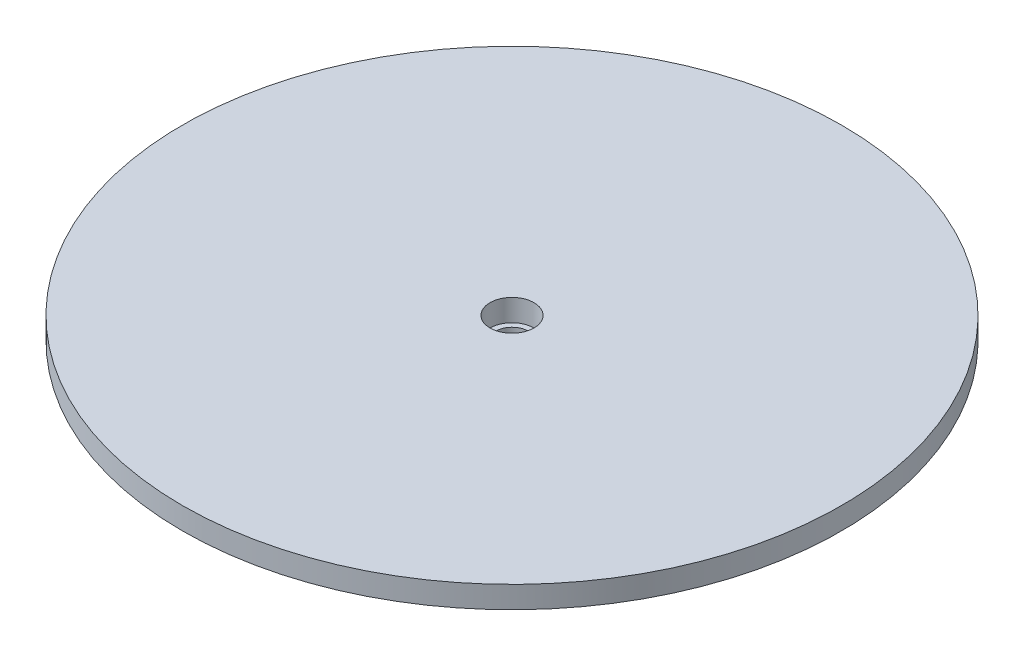
SolidWorks part; units mm, degrees
ref_plane "前视基准面" through (0, 0, 0) normal (0, 0, 1) x (1, 0, 0)
ref_plane "上视基准面" through (0, 0, 0) normal (0, 1, 0) x (1, 0, 0)
ref_plane "右视基准面" through (0, 0, 0) normal (1, 0, 0) x (0, 0, -1)
other "Configuration Table"
sketch "草图1" plane through (0, 0, 0) normal (0, 1, 0) x (1, 0, 0)
  circle A0 centre (0, 0) radius 10
  circle A1 centre (0, 0) radius 30
  circle A2 centre (0, 0) radius 2
  circle A3 centre (0, 0) radius 1
  circle A4 centre (0, 0) radius 1.5
  dimension "D3" = 20
  dimension "D5" = 3
  dimension "D1" = 60
  dimension "D2" = 2
  dimension "D4" = 4
extrude "凸台-拉伸1" add sketch "草图1" along normal blind 2 contours A1
sketch "草图2" plane through (0, 0, 0) normal (0, -1, 0) x (1, 0, 0)
  line L1 (-3, -3) -> (3, -3)
  line L2 (-3, -3) -> (-3, 3)
  line L3 (-3, 3) -> (3, 3)
  line L4 (3, -3) -> (3, 3)
  line L5 (-3, -3) -> (3, 3) construction
  line L6 (-3, 3) -> (3, -3) construction
  point P0 (0, 0)
  dimension "D1" = 6
extrude "凸台-拉伸2" add sketch "草图2" along normal blind 2
extrude "切除-拉伸1" cut sketch "草图1<10>" against normal through all both and the other way through all contours A4
sketch "草图1<10>" plane through (0, 0, 0) normal (0, 1, 0) x (1, 0, 0) same geometry as "草图1"
extrude "切除-拉伸2" cut sketch "草图1<11>" against normal blind 2 from surface contours A2 starting at face at (0, 2, 1.5)
sketch "草图1<11>" plane through (0, 0, 0) normal (0, 1, 0) x (1, 0, 0) same geometry as "草图1"
